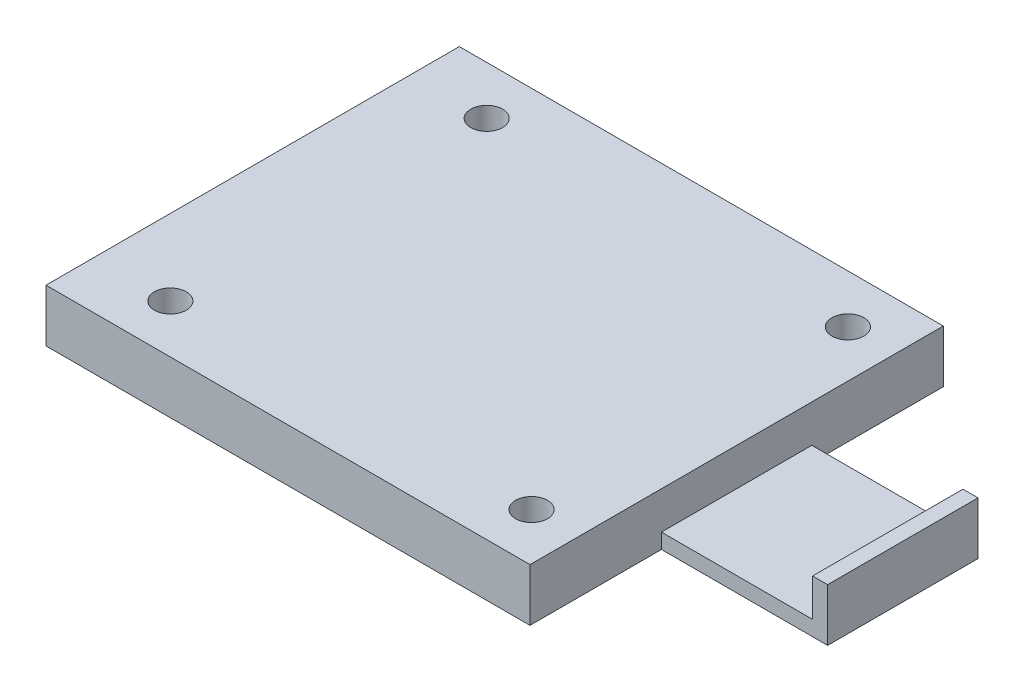
SolidWorks part; units mm, degrees
ref_plane "Front Plane" through (0, 0, 0) normal (0, 0, 1) x (1, 0, 0)
ref_plane "Top Plane" through (0, 0, 0) normal (0, 1, 0) x (1, 0, 0)
ref_plane "Right Plane" through (0, 0, 0) normal (1, 0, 0) x (0, 0, -1)
sketch "Sketch1" plane through (0, 0, 0) normal (0, 1, 0) x (1, 0, 0)
  line L0 (-28.5, 23.9839) -> (28.5, 23.9839)
  line L5 (32.1853, 10) -> (32.1853, -10)
  line L6 (-32.1853, 27.4839) -> (32.1853, 27.4839)
  line L7 (-28.5, 23.9839) -> (-28.5, -24.0161)
  line L8 (-28.5, -24.0161) -> (28.5, -24.0161)
  line L9 (28.5, 23.9839) -> (28.5, -24.0161)
  line L10 (-32.1853, 27.4839) -> (-32.1853, -27.4839)
  line L11 (-32.1853, -27.4839) -> (32.1853, -27.4839)
  line L12 (32.1853, 27.4839) -> (32.1853, -27.4839)
  line L13 (0, -27.4839) -> (0, 27.4839) construction
  line L14 (-32.1853, 0) -> (32.1853, 0) construction
  line L15 (32.1853, -10) -> (52.2853, -10)
  line L16 (52.2853, -10) -> (54.2853, -10)
  line L17 (54.2853, -10) -> (54.2853, 10)
  line L18 (54.2853, 10) -> (32.1853, 10)
  line L19 (52.2853, -10) -> (52.2853, 10)
  circle A0 centre (25.9455, 21.035) radius 2.125
  circle A1 centre (-22.0945, 21.035) radius 2.125
  circle A2 centre (-22.0945, -21.035) radius 2.125
  circle A3 centre (25.9455, -21.035) radius 2.125
  point P0 (0, 0)
  point P1 (0, 0)
  point P20 (32.1853, 0)
  dimension "D7" = 4.25
  dimension "D8" = 4.25
  dimension "D15" = 4.25
  dimension "D16" = 4.25
  dimension "D1" = 10
  dimension "D2" = 20.1
  dimension "D3" = 2
  dimension "D4" = 3.5
  dimension "D5" = 48
  dimension "D6" = 57
  dimension "D9" = 2.9489
  dimension "D10" = 6.4055
  dimension "D11" = 28.5
  dimension "D12" = 24.0161
  dimension "D13" = 22.0945
  dimension "D14" = 25.9455
extrude "Boss-Extrude1" add sketch "Sketch1" along normal blind 7 contours L12 L6 L10 L11 L5 L0 L9 L8 L7 | L19 L16 L17 L18 | L9 L0 L7 L8 A3 A2 A1 A0 region at (-0.0408, 0, 0.0164) region at (31.3388, 0, 0) region at (53.2853, 0, 0)
extrude "Boss-Extrude2" add sketch "Sketch1<3>" along normal blind 2 contours L15 L19 L18 L5 region at (42.2353, 0, 0)
sketch "Sketch1<3>" plane through (0, 0, 0) normal (0, 1, 0) x (1, 0, 0) same geometry as "Sketch1"
